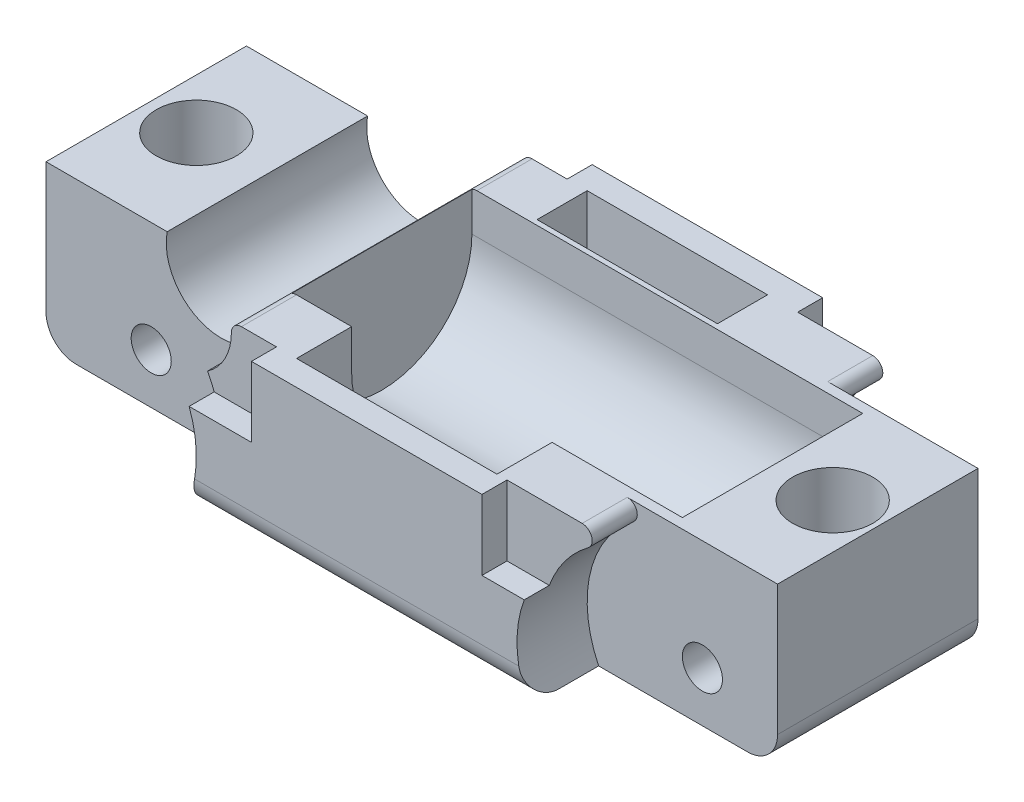
SolidWorks part; units mm, degrees
material "ABS"
ref_plane "Front Plane" through (0, 0, 0) normal (0, 0, 1) x (1, 0, 0)
ref_plane "Top Plane" through (0, 0, 0) normal (0, 1, 0) x (1, 0, 0)
ref_plane "Right Plane" through (0, 0, 0) normal (1, 0, 0) x (0, 0, -1)
sketch "Sketch1" plane through (0, 0, 0) normal (0, 1, 0) x (1, 0, 0)
  line L1 (-36.5, 17) -> (36.5, 17)
  line L2 (-36.5, 17) -> (-36.5, -17)
  line L3 (-36.5, -17) -> (36.5, -17)
  line L4 (36.5, 17) -> (36.5, -17)
  line L5 (-36.5, 17) -> (36.5, -17) construction
  line L6 (-36.5, -17) -> (36.5, 17) construction
  point P0 (0, 0)
  dimension "D1" = 73
  dimension "D2" = 34
extrude "Boss-Extrude1" add sketch "Sketch1" along normal blind 16
sketch "Sketch2" plane through (0, 0, 0) normal (0, 0, 1) x (1, 0, 0)
  point P0 (-26, 5)
  point P1 (29, 5)
  point P2 (0, 0)
  dimension "D1" = 55
  dimension "D2" = 29
  dimension "D3" = 5
sketch "Sketch3" plane through (0, 0, 0) normal (0, 0, 1) x (1, 0, 0)
  line L0 (29, 16.5) -> (40.5, 16.5)
  line L1 (40.5, 16.5) -> (40.5, 5)
  line L2 (40.5, 5) -> (40.5, -6.5)
  line L3 (40.5, -6.5) -> (29, -6.5)
  line L4 (-26, -6.5) -> (-37.5, -6.5)
  line L5 (-37.5, -6.5) -> (-37.5, 16.5)
  line L6 (-37.5, 16.5) -> (-26, 16.5)
  circle A0 centre (-26, 5) radius 11.5
  circle A1 centre (29, 5) radius 11.5
  dimension "D1" = 23
extrude "Cut-Extrude2" cut sketch "Sketch3" along normal blind 10 from offset 10 contours A1 L3 L2 | A1 | A1 L1 L0 | A0 | A0 L5 L4 | A0 L6 L5 region at (37.9313, 13.9313, 0) region at (29, 5, 0) region at (37.9313, -3.9313, 0) region at (-26, 5, 0) region at (-34.9313, -3.9313, 0) region at (-34.9313, 13.9313, 0)
mirror "Mirror1" about plane through (0, 0, 0) normal (0, 0, 1) of "Cut-Extrude2"
sketch "Sketch5" plane through (0, 0, 0) normal (0, 0, 1) x (1, 0, 0)
  circle A0 centre (29, 5) radius 2
  circle A1 centre (-26, 5) radius 2
  point P6 (0, 0)
  dimension "D1" = 4
extrude "Cut-Extrude3" cut sketch "Sketch5" against normal through all both and the other way through all
sketch "Sketch4" plane through (0, 0, 0) normal (1, 0, 0) x (0, 0, -1)
  line L0 (-9, 12) -> (-9, 23.0528)
  line L1 (-9, 23.0528) -> (9, 23.0528)
  line L2 (9, 23.0528) -> (9, 12)
  circle A0 centre (0, 12) radius 9
  dimension "D1" = 18
  dimension "D2" = 12
extrude "Battery" add sketch "Sketch4" along normal blind 26 and the other way blind 13 separate body contours A0 | A0 L2 L1 L0 region at (0, 17.5264, 8.7888) region at (0, 12, 0)
combine bodies "Combine1" operation type subtract main body 106 bodies to subtract 104
sketch "Sketch13" plane through (0, 16, 0) normal (0, 1, 0) x (1, 0, 0)
  circle A0 centre (32, 0) radius 4
  circle A1 centre (-31.5, 0) radius 4
  dimension "D1" = 8
  dimension "D3" = 5.5
  dimension "D2" = 3
extrude "MountHole" cut sketch "Sketch13" against normal blind 6
sketch "Sketch6" plane through (0, 0, 0) normal (0, 1, 0) x (1, 0, 0)
  line L1 (11, 9.5) -> (-7, 9.5)
  line L2 (11, 9.5) -> (11, 14.5)
  line L3 (11, 14.5) -> (-7, 14.5)
  line L4 (-7, 9.5) -> (-7, 14.5)
  line L5 (11, 9.5) -> (-7, 14.5) construction
  line L6 (11, 14.5) -> (-7, 9.5) construction
  point P0 (2, 12)
  point P5 (0, 0)
  point P6 (0, 0)
  dimension "D1" = 18
  dimension "D2" = 5
  dimension "D3" = 12
  dimension "D4" = 2
extrude "Charger" cut sketch "Sketch6" along normal up to next from offset 3
sketch "Sketch7" plane through (0, 0, 0) normal (0, -1, 0) x (1, 0, 0)
  line L1 (7.5, -16) -> (-3.5, -16)
  line L2 (7.5, -16) -> (7.5, -8)
  line L3 (7.5, -8) -> (-3.5, -8)
  line L4 (-3.5, -16) -> (-3.5, -8)
  line L5 (7.5, -16) -> (-3.5, -8) construction
  line L6 (7.5, -8) -> (-3.5, -16) construction
  point P0 (2, -12)
  dimension "D1" = 11
  dimension "D2" = 8
extrude "MicroUSB" cut sketch "Sketch7" against normal blind 3
fillet "Fillet1" radius 1.5 2 edges at (2, 3, -16) (2, 3, -8)
sketch "Sketch8" plane through (0, 0, 0) normal (0, 0, 1) x (1, 0, 0)
  circle A0 centre (-19, 15) radius 5.5
  dimension "D1" = 11
  dimension "D2" = 19
  dimension "D3" = 15
extrude "Motor" cut sketch "Sketch8" against normal through all both and the other way through all
fillet "BottomFillet_3mm" radius 3 4 edges at (1.5, 0, 17) (1.5, 0, -17) (36.5, 0, 0) (-36.5, 0, 0)
fillet "Fillet_1mm" radius 1 3 edges at (25.6459, 16, 13.5) (25.6459, 16, -13.5) (-13.5917, 16, 0)
sketch "Sketch10" plane through (0, 16, 0) normal (0, 1, 0) x (1, 0, 0)
  line L0 (-12.5, -17) -> (21.5, -17) construction
  line L1 (-7, -8.5) -> (13, -8.5)
  line L2 (-7, -8.5) -> (-7, -14.5)
  line L3 (-7, -14.5) -> (13, -14.5)
  line L4 (13, -8.5) -> (13, -14.5)
  line L5 (-7, -8.5) -> (13, -14.5) construction
  line L6 (-7, -14.5) -> (13, -8.5) construction
  point P0 (3, -11.5)
  point P7 (0, 0)
  dimension "D1" = 20
  dimension "D2" = 6
  dimension "D3" = 2.5
extrude "ControlBoard" cut sketch "Sketch10" against normal blind 12
fillet "Fillet2" radius 2 1 edges at (3, 9.042, 8.5)
hole_wizard "CSK for M3 Flat Head Machine Screw1" positions "Sketch11" profile "Sketch12" countersink size "M3" standard "ANSI Metric"
sketch "Sketch11" plane through (0, 0, 0) normal (0, -1, 0) x (-1, 0, 0)
  point P0 (-32, 0)
  point P5 (31.5, 0)
sketch "Sketch12" plane through (32, 0, 0) normal (1, 0, 0) x (0, 0, -1)
  line L0 (0, 0) -> (0, 11.0815)
  line L1 (0, 11.0815) -> (1.8, 10)
  line L2 (1.8, 10) -> (1.8, 1.35)
  line L3 (1.8, 1.35) -> (3.15, 0)
  line L5 (3.15, 0) -> (0, 0)
  line L6 (-1.8, 1.35) -> (-3.15, 0) construction
  line L10 (0, 11.0815) -> (-1.8, 10) construction
  line L11 (0, -6.35) -> (0, 107.95) construction
  dimension "Hole Dia." = 3.6
  dimension "Hole Depth" = 10
  dimension "Near C'Sink Dia." = 6.3
  dimension "Near C'Sink Angle" = 90
  dimension "Drill Angle" = 118
sketch "Sketch14" plane through (0, 0, 0) normal (0, 0, 1) x (1, 0, 0)
  line L1 (25.8393, 9) -> (14, 9)
  line L2 (25.8393, 9) -> (25.8393, 23.5989)
  line L3 (25.8393, 23.5989) -> (14, 23.5989)
  line L4 (14, 9) -> (14, 23.5989)
  line L5 (-22.7748, 9) -> (-9, 9)
  line L6 (-22.7748, 9) -> (-22.7748, 22.7145)
  line L7 (-22.7748, 22.7145) -> (-9, 22.7145)
  line L8 (-9, 9) -> (-9, 22.7145)
  dimension "D1" = 14
  dimension "D2" = 9
  dimension "D3" = 9
extrude "Cut-Extrude5" cut sketch "Sketch14" along normal blind 2.5 from vertex starting at point (21.5, 16, -17)
extrude "Cut-Extrude6" cut sketch "Sketch14<2>" against normal blind 2.5 from vertex starting at point (21.5, 16, 17)
sketch "Sketch14<2>" plane through (0, 0, 0) normal (0, 0, 1) x (1, 0, 0) same geometry as "Sketch14"
